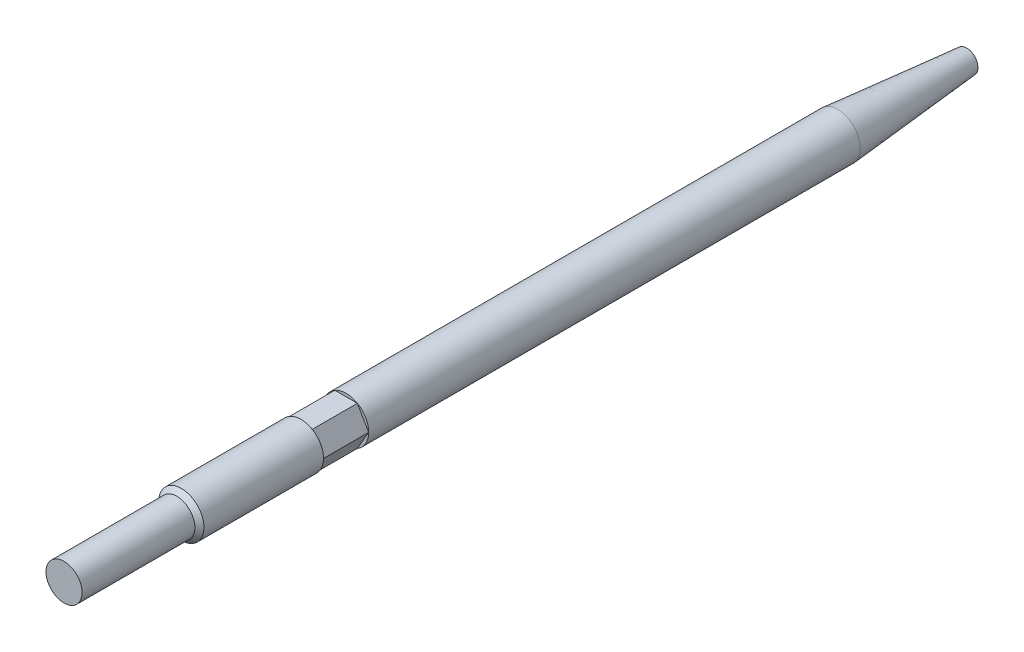
SolidWorks part; units mm, degrees
ref_plane "Front" through (0, 0, 0) normal (0, 0, 1) x (1, 0, 0)
ref_plane "Top" through (0, 0, 0) normal (0, 1, 0) x (1, 0, 0)
ref_plane "Right" through (0, 0, 0) normal (1, 0, 0) x (0, 0, -1)
sketch "Sketch1" plane through (0, 0, 0) normal (0, 0, 1) x (1, 0, 0)
  circle A0 centre (0, 0) radius 10
  dimension "D1" = 20
extrude "Extrude1" add sketch "Sketch1" along normal mid plane 1000
chamfer "Chamfer1" distance 2 angle 45 2 edges at (10, 0, -500) (10, 0, 500)
sketch "Sketch2" plane through (0, 0, 500) normal (0, 0, 1) x (1, 0, 0)
  circle A0 centre (0, 0) radius 43.0131
  circle A1 centre (0, 0) radius 8
  dimension "D1" = 16
extrude "Cut-Extrude1" cut sketch "Sketch2" against normal blind 50
chamfer "Chamfer2" distance 2 angle 45 1 edges at (10, 0, 450)
sketch "Sketch3" plane through (0, 0, -500) normal (0, 0, -1) x (-1, 0, 0)
  circle A0 centre (0, 0) radius 224.6223
extrude "remove" cut sketch "Sketch3" against normal blind 600
ref_plane "Plane1" through (0, 0, 395) normal (0, 0, 1) x (1, 0, 0)
sketch "Sketch4" plane through (0, 0, 395) normal (0, 0, 1) x (1, 0, 0)
  line L1 (5, 8.6603) -> (-5, 8.6603)
  line L2 (-5, 8.6603) -> (-10, 0)
  line L3 (-10, 0) -> (-5, -8.6603)
  line L4 (-5, -8.6603) -> (5, -8.6603)
  line L5 (5, -8.6603) -> (10, 0)
  line L6 (10, 0) -> (5, 8.6603)
  circle A0 centre (0, 0) radius 8.6603 construction
  circle A1 centre (0, 0) radius 20
  dimension "D2" = 40
  dimension "D1" = 20
extrude "hex" cut sketch "Sketch4" against normal blind 20
chamfer "Chamfer3" distance 5 angle 85 1 edges at (-10, 0, 100) first distance on face at (-10, 0, 100)
equation "\"D1@Chamfer1\" = \"D1@Sketch1\" * .1"
